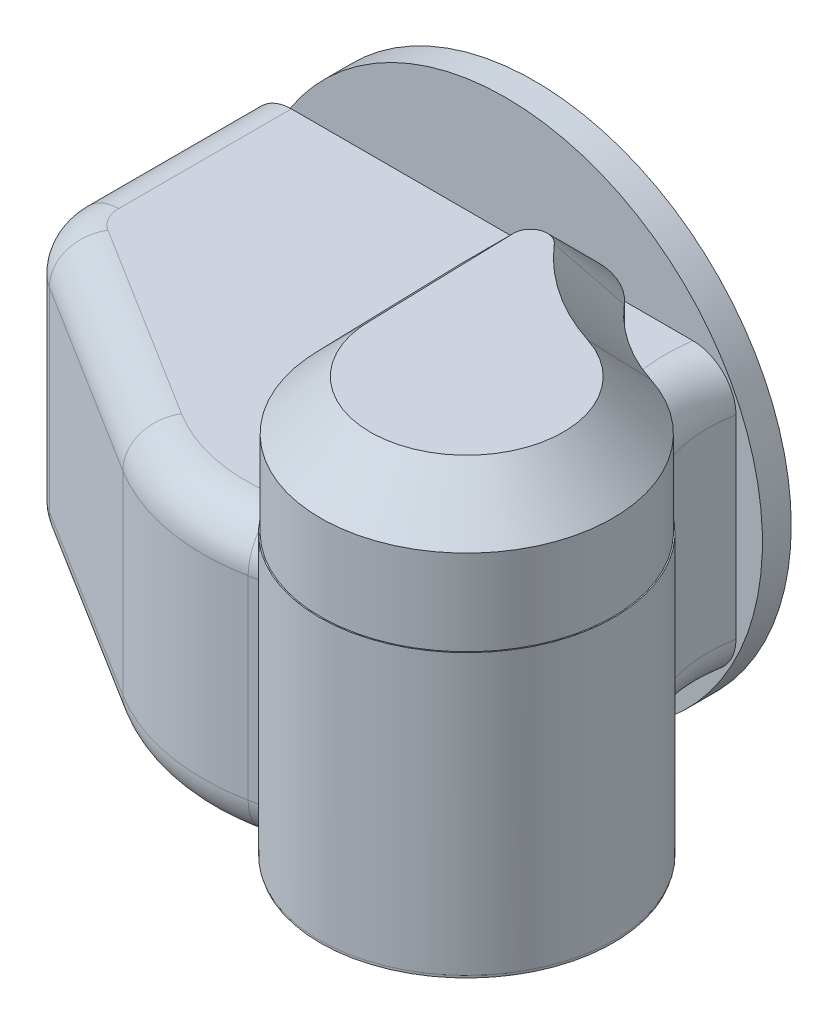
SolidWorks part; units mm, degrees
ref_plane "前基準面" through (0, 0, 0) normal (0, 0, 1) x (1, 0, 0)
ref_plane "上基準面" through (0, 0, 0) normal (0, 1, 0) x (1, 0, 0)
ref_plane "右基準面" through (0, 0, 0) normal (1, 0, 0) x (0, 0, -1)
sketch "草圖1" plane through (0, 0, 0) normal (0, 0, 1) x (1, 0, 0)
  arc A0 (179.0165, 26.7225) -> (179.0165, -26.7228) centre (0, 0) ccw construction
  arc A1 (179.0165, 26.7225) -> (179.0165, -26.7228) centre (0, 0) ccw construction
  circle A2 centre (0, 0) radius 181
extrude "填料-伸長1" add sketch "草圖1" along normal blind 20.3
sketch "草圖2" plane through (0, 0, 0) normal (0, 1, 0) x (1, 0, 0)
  line L0 (-181, -20.3) -> (181, -20.3) construction
  line L1 (162.3273, -20.3) -> (-181, -20.3)
  line L2 (-181, -20.3) -> (-181, -142.0069)
  line L3 (-157.4832, -184.4173) -> (-19.5753, -270.5339)
  line L4 (88.7297, -290.5011) -> (94.8301, -289.3052)
  arc A0 (94.8301, -289.3052) -> (204.4626, -119.3589) centre (169.33, -217.03) ccw
  arc A1 (-141.681, -183.7414) -> (1.6711, -276.8159) centre (198.2681, 182.9119) ccw construction
  arc A3 (204.4626, -119.3589) -> (162.3273, -20.3) centre (257.5808, -38.274) cw
  arc A4 (-19.5753, -270.5339) -> (88.7297, -290.5011) centre (59.8742, -143.3027) ccw
  arc A5 (-181, -142.0069) -> (-157.4832, -184.4173) centre (-131, -142.0069) ccw
  dimension "D1" = 150
  dimension "D2" = 50
  dimension "D4" = 96.9345
  dimension "D3" = 257.5808
  dimension "D5" = 38.274
  dimension "D6" = 121.7069
  dimension "D7" = 270.5339
extrude "填料-伸長2" add sketch "草圖2" against normal blind 98.5 and the other way blind 98.5
sketch "草圖3" plane through (0, -98.5, 0) normal (0, -1, 0) x (1, 0, 0)
  arc A0 (147.7969, 116.1015) -> (269.9496, 194.0967) centre (169.33, 217.03) ccw construction
  arc A1 (147.7969, 116.1015) -> (269.9496, 194.0967) centre (169.33, 217.03) ccw construction
  circle A2 centre (169.33, 217.03) radius 103.2
extrude "填料-伸長3" add sketch "草圖3" along normal blind 2
sketch "草圖4" plane through (0, 98.5, 0) normal (0, 1, 0) x (1, 0, 0)
  line L0 (66.33, -217.03) -> (63.456, -114.3938)
  arc A0 (66.33, -217.03) -> (200.781, -118.9492) centre (169.33, -217.03) ccw
  arc A1 (145.8765, -82.5316) -> (63.456, -114.3938) centre (110.3177, -113.0816) ccw
  arc A4 (145.8765, -82.5316) -> (200.781, -118.9492) centre (237.7771, -3.576) ccw
  dimension "D1" = 93.76
  dimension "D2" = 206
  dimension "D3" = 168.0397
extrude "填料-伸長4" add sketch "草圖4" along normal blind 95.2
chamfer "導角1" distance 35 angle 45 4 edges at (64.893, 193.7, 165.7119) (230.0323, 193.7, 300.2419) (93.4139, 193.7, 69.3552) (170.8058, 193.7, 104.544)
fillet "圓角1" radius 30 12 edges at (-181, -98.5, 81.1535) (-174.7273, -98.5, 166.254) (91.7799, -98.5, 289.9032) (32.6784, -98.5, 290.8168) (-181, 98.5, 81.1535) (-174.7273, 98.5, 166.254) (91.7799, 98.5, 289.9032) (32.6784, 98.5, 290.8168) (168.3804, -98.5, 76.216) (168.3804, 98.5, 76.216) (-88.5293, -98.5, 227.4756) (-88.5293, 98.5, 227.4756)
